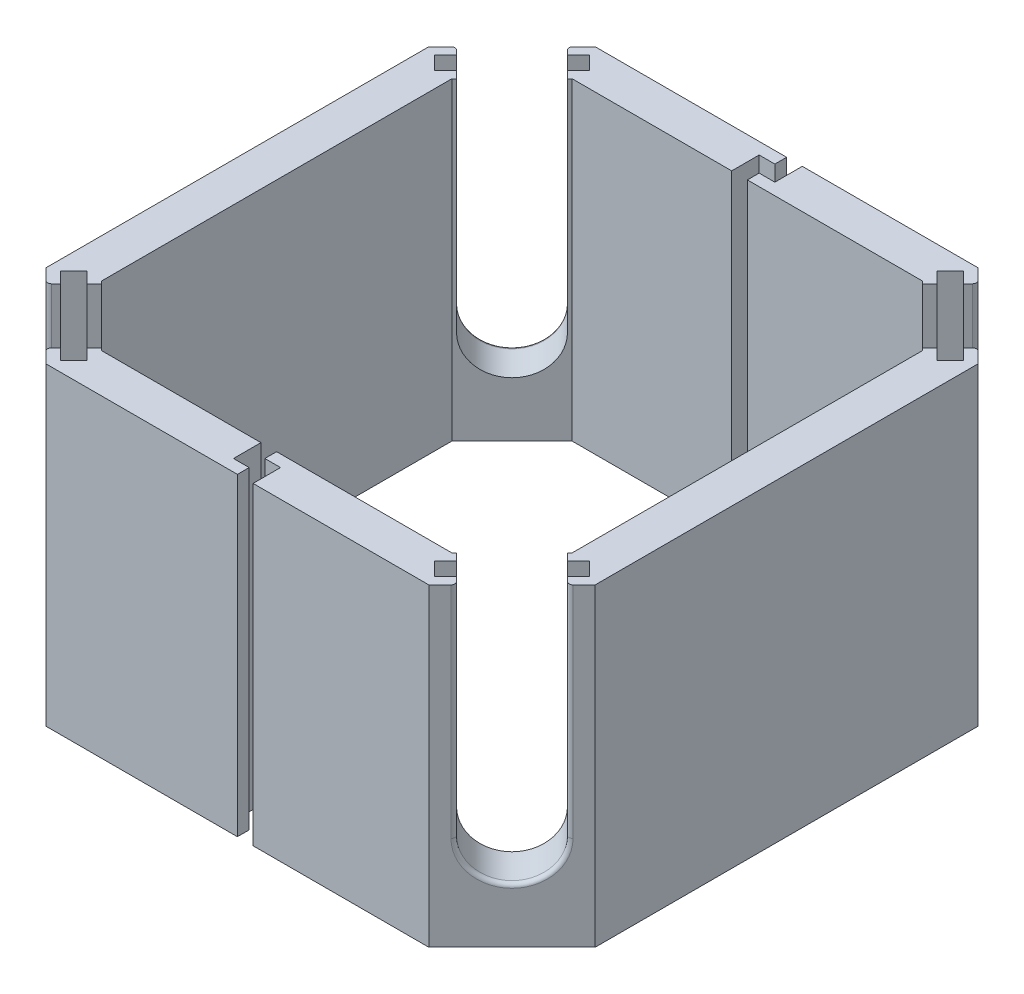
SolidWorks part; units mm, degrees
ref_plane "Front Plane" through (0, 0, 0) normal (0, 0, 1) x (1, 0, 0)
ref_plane "Top Plane" through (0, 0, 0) normal (0, 1, 0) x (1, 0, 0)
ref_plane "Right Plane" through (0, 0, 0) normal (1, 0, 0) x (0, 0, -1)
sketch "Sketch1" plane through (0, 0, 0) normal (0, 1, 0) x (1, 0, 0)
  line L0 (-12.1967, 17.5) -> (-17.5, 12.1967)
  line L1 (12.1967, -17.5) -> (-12.1967, -17.5)
  line L2 (17.5, -12.1967) -> (17.5, 12.1967)
  line L3 (12.1967, 17.5) -> (-12.1967, 17.5)
  line L4 (-17.5, -12.1967) -> (-17.5, 12.1967)
  line L5 (14.8483, -14.8483) -> (-14.8483, 14.8483) construction
  line L6 (14.8483, 14.8483) -> (-14.8483, -14.8483) construction
  line L7 (-17.5, -12.1967) -> (-12.1967, -17.5)
  line L8 (12.1967, 17.5) -> (17.5, 12.1967)
  line L9 (17.5, -12.1967) -> (12.1967, -17.5)
  line L10 (0, 17.5) -> (0, 0) construction
  line L11 (0, 0) -> (0, -17.5) construction
  line L12 (-17.5, 0) -> (0, 0) construction
  line L13 (0, 0) -> (17.5, 0) construction
  point P0 (0, 0)
  dimension "D1" = 7.5
  dimension "D2" = 35
extrude "Boss-Extrude1" add sketch "Sketch1" along normal blind 20
sketch "Sketch2" plane through (0, 20, 0) normal (0, 1, 0) x (1, 0, 0)
  line L0 (-12.1967, 17.5) -> (-17.5, 12.1967) construction
  line L1 (-17.5, 12.1967) -> (-17.5, -12.1967) construction
  line L2 (-17.5, -12.1967) -> (-12.1967, -17.5) construction
  line L3 (-12.1967, -17.5) -> (12.1967, -17.5) construction
  line L4 (12.1967, -17.5) -> (17.5, -12.1967) construction
  line L5 (17.5, -12.1967) -> (17.5, 12.1967) construction
  line L6 (17.5, 12.1967) -> (12.1967, 17.5) construction
  line L7 (-12.1967, 17.5) -> (12.1967, 17.5) construction
  line L9 (-11.1612, 15) -> (-15, 11.1612)
  line L10 (-15, 11.1612) -> (-15, -11.1612)
  line L11 (-15, -11.1612) -> (-11.1612, -15)
  line L12 (-11.1612, -15) -> (11.1612, -15)
  line L13 (11.1612, -15) -> (15, -11.1612)
  line L14 (15, -11.1612) -> (15, 11.1612)
  line L15 (15, 11.1612) -> (11.1612, 15)
  line L16 (-11.1612, 15) -> (11.1612, 15)
  dimension "D1" = 2.5
extrude "Cut-Extrude1" cut sketch "Sketch2" against normal up to next
ref_plane "Plane3" through (0, 0, 0) normal (0, -1, 0) x (-1, 0, 0)
ref_axis "Axis1" through (0, 0, 0) along (0, -1, 0)
sketch "Sketch4" plane through (14.8483, 0, 14.8483) normal (0.7071, 0, 0.7071) x (0.7071, 0, -0.7071)
  line L0 (0, 20) -> (0, 0) construction
  line L1 (-3.75, 20) -> (3.75, 20) construction
  line L2 (-2.5, 20) -> (2.5, 20)
  line L3 (-3.75, 0) -> (3.75, 0) construction
  line L4 (-2.5, 6) -> (-2.5, 20)
  line L6 (2.5, 6) -> (2.5, 20)
  arc A0 (-2.5, 6) -> (2.5, 6) centre (0, 6) ccw
  dimension "D1" = 2.5
  dimension "D2" = 14
extrude "Cut-Extrude2" cut sketch "Sketch4" against normal up to next
ref_plane "Plane1" through (0, 0, 0) normal (0.7071, 0, -0.7071) x (-0.7071, 0, -0.7071)
pattern_circular "CirPattern3" count 4 over 360 about axis through (0, 0, 0) along (0, -1, 0) of "Cut-Extrude2"
sketch "Sketch5" plane through (0, 20, 0) normal (0, 1, 0) x (1, 0, 0)
  line L0 (11.3128, -14.8483) -> (12.1967, -15.7322) construction
  line L2 (11.3128, -14.8483) -> (13.0806, -16.6161) construction
  line L3 (12.1967, -15.7322) -> (13.0806, -16.6161) construction
  line L4 (11.7724, -15.308) -> (12.621, -16.1565)
  line L5 (-12.1967, -17.5) -> (12.1967, -17.5) construction
  line L7 (11.7724, -15.308) -> (11.0653, -16.0151)
  line L8 (12.621, -16.1565) -> (11.9139, -16.8636)
  line L9 (11.0653, -16.0151) -> (11.9139, -16.8636)
  dimension "D1" = 1.2
  dimension "D2" = 1
extrude "Cut-Extrude3" cut sketch "Sketch5" against normal blind 14
mirror "Mirror1" about plane through (0, 0, 0) normal (0.7071, 0, -0.7071) of "Cut-Extrude3"
pattern_circular "CirPattern4" count 4 over 360 about axis through (0, 0, 0) along (0, -1, 0) of "Cut-Extrude3", "Mirror1"
fillet "Fillet1" radius 0.25 12 edges at (16.6161, 13, 13.0806) (14.8483, 3.5, 14.8483) (13.0806, 13, 16.6161) (-13.0806, 13, -16.6161) (-14.8483, 3.5, -14.8483) (-16.6161, 13, -13.0806) (16.6161, 13, -13.0806) (14.8483, 3.5, -14.8483) (-13.0806, 13, 16.6161) (-14.8483, 3.5, 14.8483) (13.0806, 13, -16.6161) (-16.6161, 13, 13.0806)
sketch "Sketch6" plane through (0, 20, 0) normal (0, 1, 0) x (1, 0, 0)
  line L0 (0, -15) -> (-0.5, -15) construction
  line L2 (-11.1612, -15) -> (11.1612, -15) construction
  line L3 (0.5, -16.25) -> (0.5, -17.5) construction
  line L4 (-12.1967, -17.5) -> (12.1967, -17.5) construction
  line L5 (-0.5, -15) -> (-0.5, -16.25) construction
  line L6 (-0.5, -16.25) -> (0.5, -16.25) construction
  line L7 (0, -17.5) -> (0.5, -17.5) construction
  line L8 (-1, -15) -> (-1, -16.75)
  line L9 (-1, -16.75) -> (0, -16.75)
  line L10 (0, -16.75) -> (0, -17.5)
  line L11 (0, -15) -> (0, -15.75)
  line L12 (0, -15.75) -> (1, -15.75)
  line L13 (1, -15.75) -> (1, -17.5)
  line L14 (-1, -15) -> (0, -15)
  line L15 (0, -17.5) -> (1, -17.5)
  line M4 (-12.1967, -17.5) -> (12.1967, -17.5)
  line M13 (11.1612, -15) -> (-11.1612, -15)
  dimension "D1" = 0.5
  dimension "D2" = 0.5
  dimension "D3" = 0.5
extrude "Cut-Extrude4" cut sketch "Sketch6" against normal through all contours L13 L12 L11 L8 L9 L10 M13 M4 region at (0, 20, 16.25)
mirror "Mirror2" about plane through (0, 0, 0) normal (0, 0, 1) of "Cut-Extrude4"
